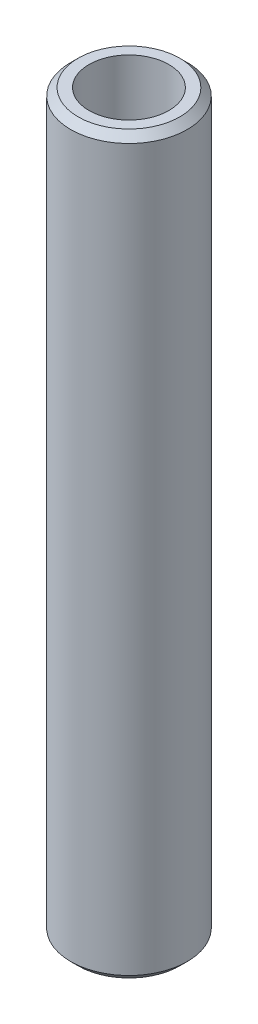
SolidWorks part; units mm, degrees
ref_plane "Front Plane" through (0, 0, 0) normal (0, 0, 1) x (1, 0, 0)
ref_plane "Top Plane" through (0, 0, 0) normal (0, 1, 0) x (1, 0, 0)
ref_plane "Right Plane" through (0, 0, 0) normal (1, 0, 0) x (0, 0, -1)
sketch "Sketch1" plane through (0, 0, 0) normal (0, 1, 0) x (1, 0, 0)
  circle A0 centre (0, 0) radius 47.5
  dimension "SHAFT_OD" = 95
extrude "Boss-Extrude1" add sketch "Sketch1" along normal blind 600
sketch "Sketch2" plane through (0, 0, 0) normal (0, 1, 0) x (1, 0, 0)
  circle A0 centre (0, 0) radius 32.5807
  dimension "BORE_D" = 65.1614
extrude "Cut-Extrude1" cut sketch "Sketch2" along normal through all
chamfer "Chamfer1" distance 5.9994 angle 45 2 edges at (0, 600, 47.5) (0, 0, 47.5)
